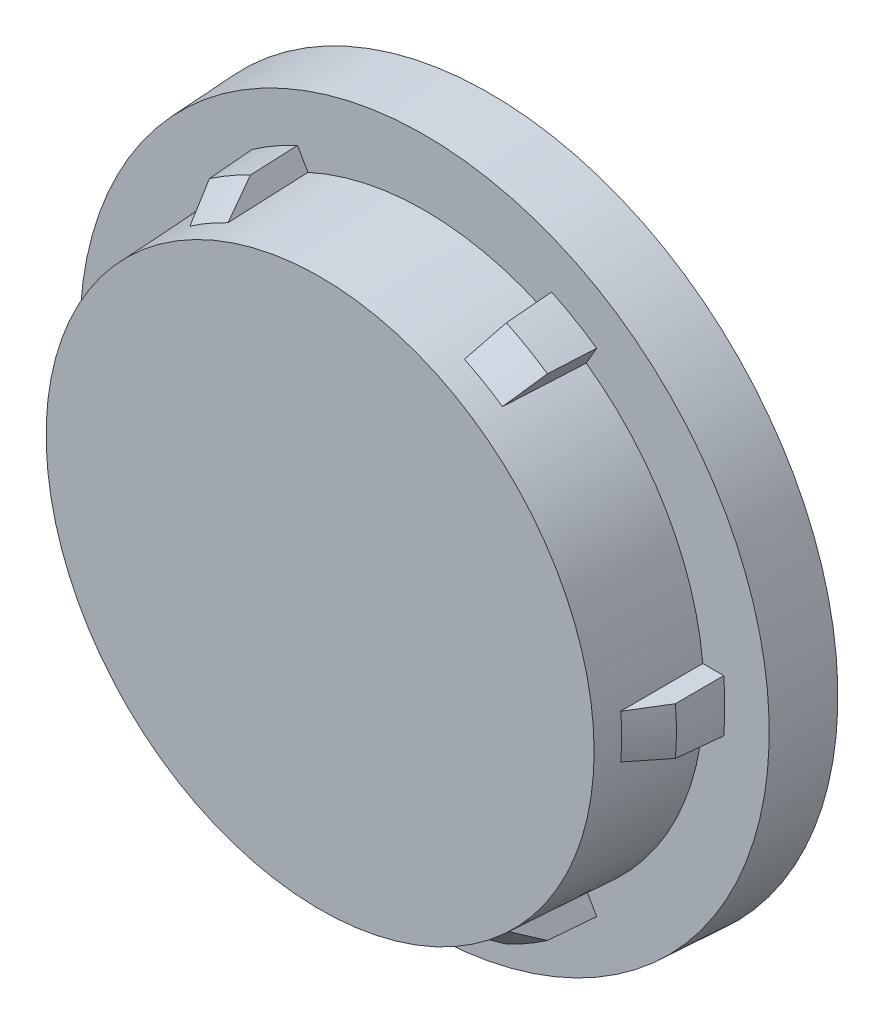
SolidWorks part; units mm, degrees
ref_plane "Front Plane" through (0, 0, 0) normal (0, 0, 1) x (1, 0, 0)
ref_plane "Top Plane" through (0, 0, 0) normal (0, 1, 0) x (1, 0, 0)
ref_plane "Right Plane" through (0, 0, 0) normal (1, 0, 0) x (0, 0, -1)
sketch "Sketch1" plane through (0, 0, 0) normal (0, 0, 1) x (1, 0, 0)
  circle A0 centre (0, 0) radius 5.25
  dimension "D1" = 10.5
extrude "Base Extrusion" add sketch "Sketch1" against normal blind 2
sketch "Sketch3" plane through (0, 0, -2) normal (0, 0, -1) x (-1, 0, 0)
  circle A0 centre (0, 0) radius 6.5
  circle A1 centre (0, 0) radius 5.25 construction
  dimension "D1" = 1.25
extrude "Lens Mounting Flange" add sketch "Sketch3" along normal blind 1.25
sketch "Sketch5" plane through (0, 0, -3.25) normal (0, 0, -1) x (-1, 0, 0)
  circle A0 centre (0, 0) radius 4.25
  dimension "D1" = 8.5
extrude "Inner Cavity" cut sketch "Sketch5" against normal offset from surface (2.25 mm away) 1 up to face at (5.25, 0, 0)
draft "Outside Draft" type of draft neutral plane draft angle 3 faces to draft 2 face at (-6.5, 0, -3.25) face at (-5.25, 0, -2) neutral plane through (0, 0, 0) neutral plane normal (0, 0, 1) parameters "D1"=3
draft "Inside Draft" type of draft neutral plane draft angle 3 faces to draft 1 face at (-4.25, 0, -3.25) neutral plane through (0, 0, -1) neutral plane normal (0, 0, -1) parameters "D1"=3
sketch "Sketch6" plane through (0, 0, -3.25) normal (0, 0, -1) x (-1, 0, 0)
  line L0 (0, 8) -> (0, -8) construction
  line L3 (-1.6, 8) -> (-1.6, 9.6)
  line L4 (-1.6, 9.6) -> (1.6, 9.6)
  line L5 (1.6, 8) -> (1.6, 9.6)
  line L6 (-1.6, -8) -> (-1.6, -9.6)
  line L7 (-1.6, -9.6) -> (1.6, -9.6)
  line L8 (1.6, -8) -> (1.6, -9.6)
  arc A0 (-1.6, 8) -> (1.6, 8) centre (0, 8) ccw
  arc A1 (1.6, -8) -> (-1.6, -8) centre (0, -8) ccw
  point P3 (0, 0)
  dimension "D1" = 3.2
  dimension "D2" = 16
extrude "Mounting Post Holes" [suppressed] cut sketch "Sketch6" against normal through all draft 3 draft outward yes
sketch "Sketch7" plane through (0, 0, -2) normal (0, 0, 1) x (1, 0, 0)
  line L0 (0, 0) -> (-6.6048, 0) construction
  line L1 (-5.7331, 0.5) -> (-4.7331, 0.5)
  line L2 (-4.7331, 0.5) -> (-4.7331, -0.5)
  line L3 (-4.7331, -0.5) -> (-5.7331, -0.5)
  circle A0 centre (0, 0) radius 6.6048 construction
  arc A2 (-5.7331, 0.5) -> (-5.7331, -0.5) centre (0, 0) ccw
  circle A3 centre (0, 0) radius 5.3548 construction
  point P0 (-4.7331, 0)
  dimension "D1" = 1
  dimension "D2" = 0.4
  dimension "D3" = 1
extrude "Interference Rib" add sketch "Sketch7" along normal blind 1.5 draft 3
chamfer "Interference Rib Chamfer" distance 0.4 angle 55 1 edges at (-5.6762, 0, -0.5) first distance on face at (-5.4681, 0, -0.5)
pattern_circular "Interference Rib Pattren" count 6 over 360 about axis through (0, 0, 0) along (0, 0, 1) of "Interference Rib", "Interference Rib Chamfer"
